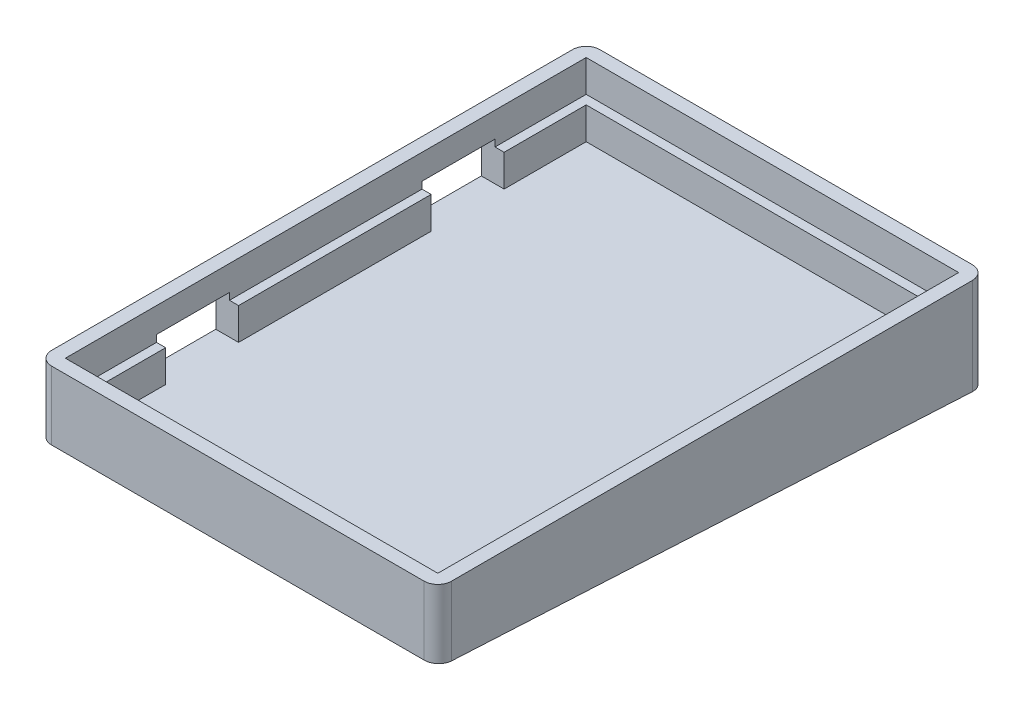
SolidWorks part; units mm, degrees
ref_plane "Front Plane" through (0, 0, 0) normal (0, 0, 1) x (1, 0, 0)
ref_plane "Top Plane" through (0, 0, 0) normal (0, 1, 0) x (1, 0, 0)
ref_plane "Right Plane" through (0, 0, 0) normal (1, 0, 0) x (0, 0, -1)
sketch "Sketch1" plane through (0, 0, 0) normal (0, 1, 0) x (1, 0, 0)
  line L0 (0, 0) -> (81.7, 0)
  line L1 (0, 0) -> (0, 114.24)
  line L2 (81.7, 0) -> (81.7, 114.24)
  line L3 (81.7, 114.24) -> (0, 114.24)
  line L4 (84.7, 117.24) -> (-3, 117.24)
  line L5 (-3, -3) -> (-3, 117.24)
  line L6 (-3, -3) -> (84.7, -3)
  line L7 (84.7, -3) -> (84.7, 117.24)
  line L8 (0, 94.24) -> (-3, 94.24)
  line L9 (-3, 94.24) -> (-3, 78.24)
  line L10 (-3, 78.24) -> (0, 78.24)
  line L11 (-3, 36) -> (0, 36)
  line L12 (-3, 20) -> (0, 20)
  dimension "D1" = 81.7
  dimension "D2" = 114.24
  dimension "D4" = 16
  dimension "D5" = 16
  dimension "D6" = 20
  dimension "D7" = 20
  dimension "D3" = 3
extrude "Boss-Extrude1" add sketch "Sketch1" along normal blind 14 contours L12 L5 L6 L7 L4 L8 L1 L3 L2 L0 | L5 L11 L1 L10 region at (40.85, 0, 1.4883) region at (-1.5, 0, -57.12)
extrude "Boss-Extrude2" add sketch "Sketch1<3>" against normal blind 1 contours L5 L10 L1 L8 | L5 L11 L1 L10 | L5 L12 L1 L11 | L2 L3 L1 L0 | L12 L5 L6 L7 L4 L8 L1 L3 L2 L0 region at (40.85, 0, -57.12) region at (40.85, 0, 1.4883) region at (-1.5, 0, -28) region at (-1.5, 0, -57.12) region at (-1.5, 0, -86.24)
sketch "Sketch1<3>" plane through (0, 0, 0) normal (0, 1, 0) x (1, 0, 0) same geometry as "Sketch1"
sketch "Sketch2" plane through (-3, 0, 0) normal (-1, 0, 0) x (0, 0, 1)
  line L0 (-117.24, -1) -> (-117.24, -7.3015)
  line L1 (-117.24, -7.3015) -> (3, -1)
  line L2 (3, -1) -> (3, 0)
  line L3 (3, 14) -> (3, -1) construction
  line L4 (3, 0) -> (-117.24, 0)
  line L5 (-117.24, 14) -> (-117.24, -1) construction
  line L6 (-117.24, 0) -> (-117.24, -1)
  line L7 (3, -1) -> (-117.24, -1) construction
  dimension "D1" = 3
extrude "Boss-Extrude3" add sketch "Sketch2" against normal up to surface (87.7 mm away) up to face at (84.7, 6.5, -57.12)
fillet "Fillet1" radius 3 4 edges at (-3, 3.3492, -117.24) (84.7, 3.3492, -117.24) (84.7, 6.5, 3) (-3, 6.5, 3)
sketch "Sketch3" plane through (0, 0, 0) normal (0, 1, 0) x (1, 0, 0)
  line L0 (2, 78.24) -> (2, 36)
  line L1 (2, 20) -> (2, 2)
  line L2 (2, 2) -> (79.7, 2)
  line L3 (79.7, 2) -> (79.7, 112.24)
  line L4 (79.7, 112.24) -> (2, 112.24)
  line L5 (2, 112.24) -> (2, 94.24)
  line L6 (2, 94.24) -> (0, 94.24)
  line L7 (2, 78.24) -> (0, 78.24)
  line L8 (2, 36) -> (0, 36)
  line L9 (2, 20) -> (0, 20)
  line L12 (0, 78.24) -> (0, 36)
  line L13 (0, 36) -> (-3, 36)
  line L14 (-3, 36) -> (-3, 20)
  line L15 (-3, 20) -> (0, 20)
  line L16 (0, 20) -> (0, 0)
  line L17 (0, 0) -> (81.7, 0)
  line L18 (81.7, 0) -> (81.7, 114.24)
  line L19 (81.7, 114.24) -> (0, 114.24)
  line L20 (0, 114.24) -> (0, 94.24)
  line L21 (0, 94.24) -> (-3, 94.24)
  line L22 (-3, 94.24) -> (-3, 78.24)
  line L23 (-3, 78.24) -> (0, 78.24)
  line L24 (0, 78.24) -> (0, 36)
  line L28 (0, 20) -> (0, 0)
  line L29 (0, 0) -> (81.7, 0)
  line L30 (81.7, 0) -> (81.7, 114.24)
  line L31 (81.7, 114.24) -> (0, 114.24)
  line L32 (0, 114.24) -> (0, 94.24)
  dimension "D1" = 0
  dimension "D2" = 2
extrude "Boss-Extrude4" add sketch "Sketch3" along normal blind 7
sketch "Sketch4" plane through (-3, 0, 0) normal (-1, 0, 0) x (0, 0, 1)
  line L0 (-78.24, 14) -> (-78.24, 0) construction
  line L1 (-94.24, 14) -> (-78.24, 14)
  line L2 (-94.24, 14) -> (-94.24, 8.5)
  line L3 (-94.24, 8.5) -> (-78.24, 8.5)
  line L4 (-78.24, 14) -> (-78.24, 8.5)
  line L5 (-20, 14) -> (-20, 0) construction
  line L6 (-36, 14) -> (-20, 14)
  line L7 (-36, 14) -> (-36, 8.5)
  line L8 (-36, 8.5) -> (-20, 8.5)
  line L9 (-20, 14) -> (-20, 8.5)
  dimension "D1" = 5.5
  dimension "D2" = 5.5
extrude "Boss-Extrude5" add sketch "Sketch4" against normal up to surface (3 mm away) up to face at (0, 10.5, -57.12)
